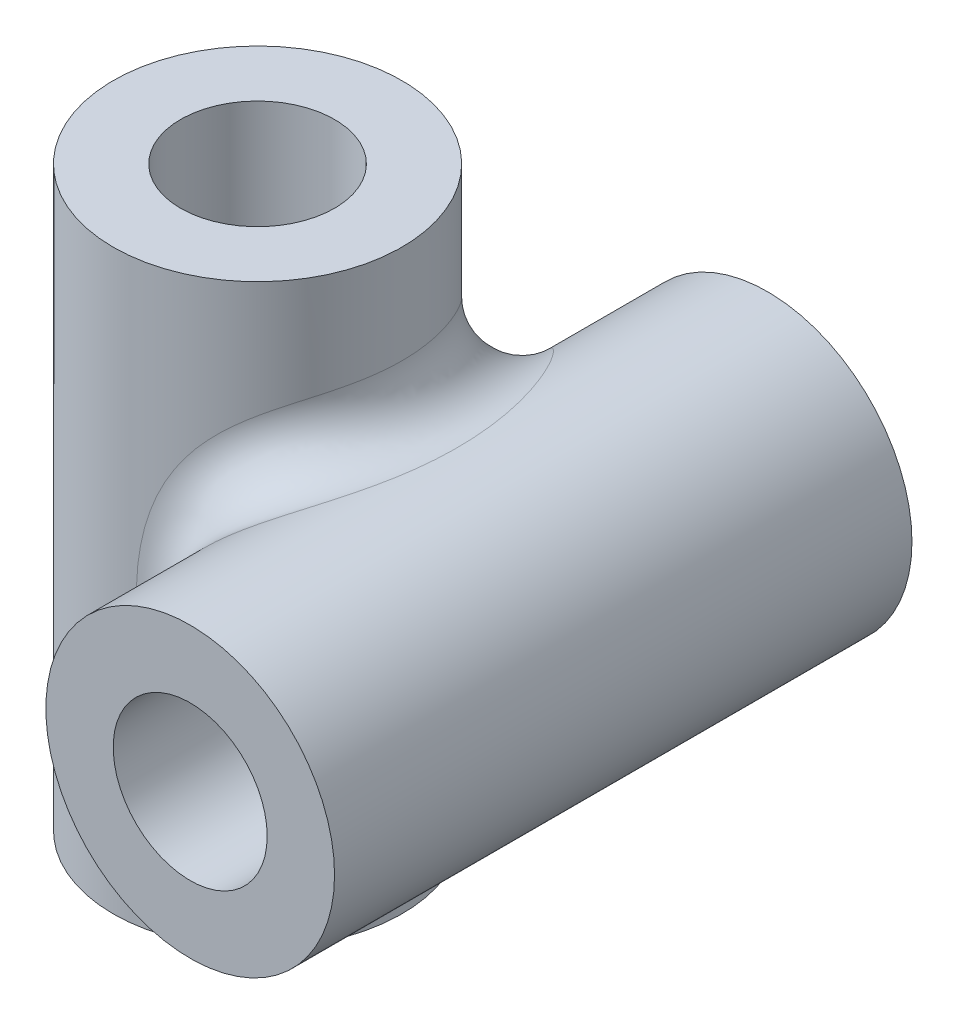
SolidWorks part; units mm, degrees
ref_plane "Front Plane" through (0, 0, 0) normal (0, 0, 1) x (1, 0, 0)
ref_plane "Top Plane" through (0, 0, 0) normal (0, 1, 0) x (1, 0, 0)
ref_plane "Right Plane" through (0, 0, 0) normal (1, 0, 0) x (0, 0, -1)
sketch "Sketch1" plane through (0, 0, 0) normal (0, 1, 0) x (1, 0, 0)
  circle A0 centre (0, 0) radius 15
  circle A1 centre (0, 0) radius 8
  dimension "D1" = 30
  dimension "D2" = 16
extrude "Boss-Extrude1" add sketch "Sketch1" along normal mid plane 60
sketch "Sketch2" plane through (0, 0, 0) normal (0, 0, 1) x (1, 0, 0)
  line L0 (-15, 30) -> (-15, -30) construction
  circle A0 centre (23, 0) radius 8
  circle A1 centre (23, 0) radius 15
  dimension "D1" = 30
  dimension "D2" = 16
  dimension "D3" = 38
extrude "Boss-Extrude2" add sketch "Sketch2" along normal mid plane 60
fillet "Fillet1" radius 5 1 edges at (8.3863, 3.3823, -12.4366)
